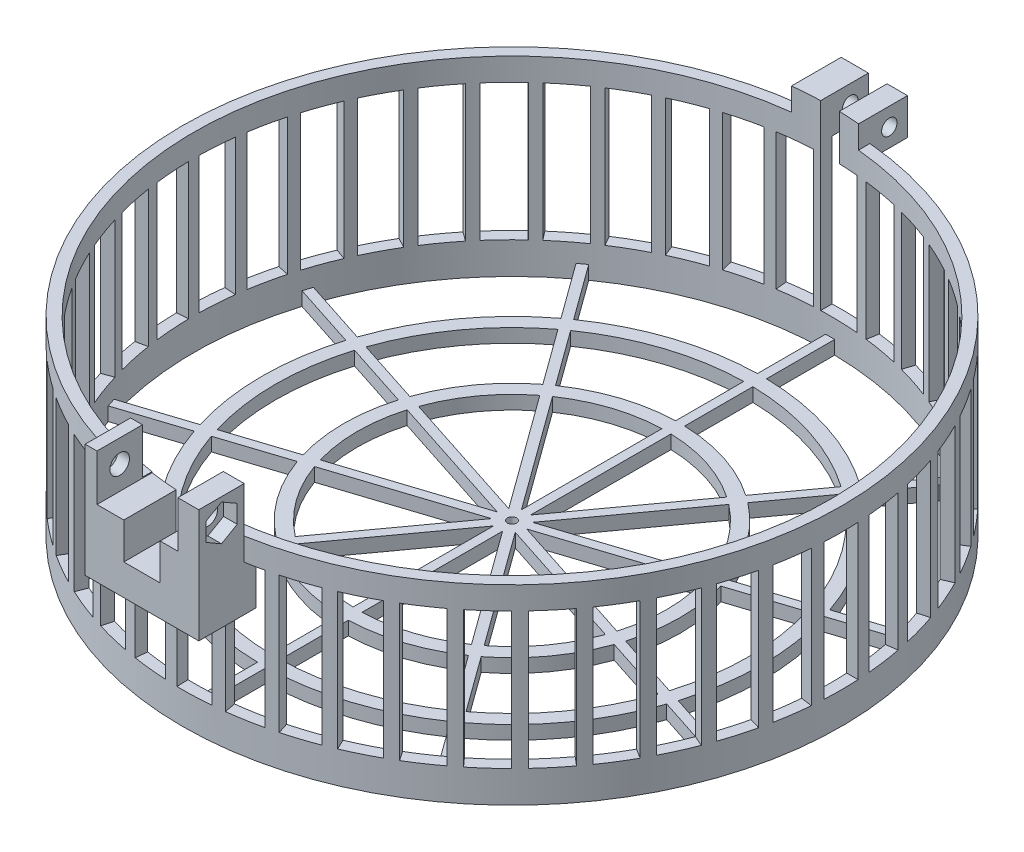
SolidWorks part; units mm, degrees
ref_plane "Front Plane" through (0, 0, 0) normal (0, 0, 1) x (1, 0, 0)
ref_plane "Top Plane" through (0, 0, 0) normal (0, 1, 0) x (1, 0, 0)
ref_plane "Right Plane" through (0, 0, 0) normal (1, 0, 0) x (0, 0, -1)
sketch "Sketch1" plane through (0, 0, 0) normal (0, 1, 0) x (1, 0, 0)
  line L0 (1, 69.9929) -> (0, 70.9924)
  line L2 (1, 69.9929) -> (1, 3.0777)
  line L4 (-1, 69.9929) -> (-1, 3.0777)
  line L5 (-0.8687, 69.9946) -> (-0.1565, 47.2626) construction
  line L7 (0, 70.9924) -> (-1, 69.9929)
  line L8 (41.7283, 57.4341) -> (40.3318, 57.2132)
  line L9 (41.9498, 56.0376) -> (41.7283, 57.4341)
  line L10 (41.9498, 56.0376) -> (2.618, 1.9021)
  line L11 (40.3318, 57.2132) -> (1, 3.0777)
  line L12 (67.5178, 21.9379) -> (66.2581, 22.58)
  line L13 (66.8762, 20.6779) -> (67.5178, 21.9379)
  line L14 (66.8762, 20.6779) -> (3.2361, 0)
  line L15 (66.2581, 22.58) -> (2.618, 1.9021)
  line L16 (67.5178, -21.9379) -> (66.8762, -20.6779)
  line L17 (66.2581, -22.58) -> (67.5178, -21.9379)
  line L18 (66.2581, -22.58) -> (2.618, -1.9021)
  line L19 (66.8762, -20.6779) -> (3.2361, 0)
  line L20 (41.7283, -57.4341) -> (41.9498, -56.0376)
  line L21 (40.3318, -57.2132) -> (41.7283, -57.4341)
  line L22 (40.3318, -57.2132) -> (1, -3.0777)
  line L23 (41.9498, -56.0376) -> (2.618, -1.9021)
  line L24 (0, -70.9924) -> (1, -69.9929)
  line L25 (-1, -69.9929) -> (0, -70.9924)
  line L26 (-1, -69.9929) -> (-1, -3.0777)
  line L27 (1, -69.9929) -> (1, -3.0777)
  line L28 (-41.7283, -57.4341) -> (-40.3318, -57.2132)
  line L29 (-41.9498, -56.0376) -> (-41.7283, -57.4341)
  line L30 (-41.9498, -56.0376) -> (-2.618, -1.9021)
  line L31 (-40.3318, -57.2132) -> (-1, -3.0777)
  line L32 (-67.5178, -21.9379) -> (-66.2581, -22.58)
  line L33 (-66.8762, -20.6779) -> (-67.5178, -21.9379)
  line L34 (-66.8762, -20.6779) -> (-3.2361, 0)
  line L35 (-66.2581, -22.58) -> (-2.618, -1.9021)
  line L36 (-67.5178, 21.9379) -> (-66.8762, 20.6779)
  line L37 (-66.2581, 22.58) -> (-67.5178, 21.9379)
  line L38 (-66.2581, 22.58) -> (-2.618, 1.9021)
  line L39 (-66.8762, 20.6779) -> (-3.2361, 0)
  line L40 (-41.7283, 57.4341) -> (-41.9498, 56.0376)
  line L41 (-40.3318, 57.2132) -> (-41.7283, 57.4341)
  line L42 (-40.3318, 57.2132) -> (-1, 3.0777)
  line L43 (-41.9498, 56.0376) -> (-2.618, 1.9021)
  line L60 (-0.1565, 47.2626) -> (0.8687, 69.9946) construction
  circle A0 centre (0, 0) radius 72.5
  circle A1 centre (0, 0) radius 70
  point P4 (0, 42.2662)
  point P59 (0, 0)
  dimension "D1" = 145
  dimension "D2" = 140
  dimension "D4" = 2
  dimension "D3" = 10
extrude "Boss-Extrude4" add sketch "Sketch1" along normal blind 16 contours A0 | A1
extrude "Boss-Extrude5" add sketch "Sketch1<11>" along normal blind 3 contours L26 L25 L24 L27 L22 L21 L20 L23 L18 L17 L16 L19 L14 L13 L12 L15 L10 L9 L8 L11 L2 L0 L7 L4 L42 L41 L40 L43 L38 L37 L36 L39 L34 L33 L32 L35 L30 L29 L28 L31
sketch "Sketch1<11>" plane through (0, 0, 0) normal (0, 1, 0) x (1, 0, 0) same geometry as "Sketch1"
sketch "Sketch2" plane through (0, 0, 0) normal (0, -1, 0) x (1, 0, 0)
  circle A0 centre (0, 0) radius 1
extrude "Cut-Extrude1" cut sketch "Sketch2" against normal through all
sketch "Sketch3" plane through (0, 0, 0) normal (0, -1, 0) x (1, 0, 0)
  circle A0 centre (0, 0) radius 52
  circle A1 centre (0, 0) radius 55
  circle A2 centre (0, 0) radius 70 construction
  circle A3 centre (0, 0) radius 37
  circle A4 centre (0, 0) radius 34
  dimension "D1" = 3
  dimension "D2" = 15
  dimension "D3" = 3
  dimension "D4" = 15
extrude "Boss-Extrude6" add sketch "Sketch3" against normal up to surface (3 mm away) contours A0 | A1 up to face at (0, 3, -1)
extrude "Boss-Extrude7" add sketch "Sketch1<12>" along normal blind 42 contours A1 | A0
sketch "Sketch1<12>" plane through (0, 0, 0) normal (0, 1, 0) x (1, 0, 0) same geometry as "Sketch1"
extrude "Boss-Extrude13" add sketch "Sketch3<5>" against normal up to surface (3 mm away) contours A3 | A4 up to face at (0, 3, 0)
sketch "Sketch3<5>" plane through (0, 0, 0) normal (0, -1, 0) x (1, 0, 0) same geometry as "Sketch3"
sketch "Sketch25" plane through (0, 42, 0) normal (0, 1, 0) x (1, 0, 0)
  line L0 (-1000, 0) -> (49000, 0) construction
  line L2 (69, 3.75) -> (74, 3.75)
  line L3 (69, 3.75) -> (69, -3.75)
  line L4 (69, -3.75) -> (74, -3.75)
  line L5 (74, 3.75) -> (74, -3.75)
  line L6 (69, 3.75) -> (74, -3.75) construction
  line L7 (69, -3.75) -> (74, 3.75) construction
  line L8 (68.8504, -5.8894) -> (73.8017, -6.5853)
  line L9 (68.8504, -5.8894) -> (67.8066, -13.3164)
  line L10 (67.8066, -13.3164) -> (72.7579, -14.0123)
  line L11 (73.8017, -6.5853) -> (72.7579, -14.0123)
  line L12 (68.8504, -5.8894) -> (72.7579, -14.0123) construction
  line L13 (67.8066, -13.3164) -> (73.8017, -6.5853) construction
  line L14 (67.3607, -15.4142) -> (72.167, -16.7924)
  line L15 (67.3607, -15.4142) -> (65.2934, -22.6237)
  line L16 (65.2934, -22.6237) -> (70.0997, -24.0019)
  line L17 (72.167, -16.7924) -> (70.0997, -24.0019)
  line L18 (67.3607, -15.4142) -> (70.0997, -24.0019) construction
  line L19 (65.2934, -22.6237) -> (72.167, -16.7924) construction
  line L20 (64.5599, -24.639) -> (69.1276, -26.6727)
  line L21 (64.5599, -24.639) -> (61.5094, -31.4906)
  line L22 (61.5094, -31.4906) -> (66.0771, -33.5243)
  line L23 (69.1276, -26.6727) -> (66.0771, -33.5243)
  line L24 (64.5599, -24.639) -> (66.0771, -33.5243) construction
  line L25 (61.5094, -31.4906) -> (69.1276, -26.6727) construction
  line L26 (60.5025, -33.3842) -> (64.7428, -36.0338)
  line L27 (60.5025, -33.3842) -> (56.5281, -39.7446)
  line L28 (56.5281, -39.7446) -> (60.7684, -42.3942)
  line L29 (64.7428, -36.0338) -> (60.7684, -42.3942)
  line L30 (60.5025, -33.3842) -> (60.7684, -42.3942) construction
  line L31 (56.5281, -39.7446) -> (64.7428, -36.0338) construction
  line L32 (55.2675, -41.4797) -> (59.0977, -44.6936)
  line L33 (55.2675, -41.4797) -> (50.4466, -47.225)
  line L34 (50.4466, -47.225) -> (54.2768, -50.4389)
  line L35 (59.0977, -44.6936) -> (54.2768, -50.4389)
  line L36 (55.2675, -41.4797) -> (54.2768, -50.4389) construction
  line L37 (50.4466, -47.225) -> (59.0977, -44.6936) construction
  line L38 (48.9568, -48.7678) -> (52.3025, -52.4835)
  line L39 (48.9568, -48.7678) -> (43.3832, -53.7862)
  line L40 (43.3832, -53.7862) -> (46.7289, -57.502)
  line L41 (52.3025, -52.4835) -> (46.7289, -57.502)
  line L42 (48.9568, -48.7678) -> (46.7289, -57.502) construction
  line L43 (43.3832, -53.7862) -> (52.3025, -52.4835) construction
  line L44 (41.6932, -55.1066) -> (44.4892, -59.2518)
  line L45 (41.6932, -55.1066) -> (35.4754, -59.3006)
  line L46 (35.4754, -59.3006) -> (38.2714, -63.4458)
  line L47 (44.4892, -59.2518) -> (38.2714, -63.4458)
  line L48 (41.6932, -55.1066) -> (38.2714, -63.4458) construction
  line L49 (35.4754, -59.3006) -> (44.4892, -59.2518) construction
  line L50 (33.6181, -60.3729) -> (35.8099, -64.8669)
  line L51 (33.6181, -60.3729) -> (26.8771, -63.6607)
  line L52 (26.8771, -63.6607) -> (29.069, -68.1547)
  line L53 (35.8099, -64.8669) -> (29.069, -68.1547)
  line L54 (33.6181, -60.3729) -> (29.069, -68.1547) construction
  line L55 (26.8771, -63.6607) -> (35.8099, -64.8669) construction
  line L56 (24.8886, -64.4641) -> (26.4337, -69.2194)
  line L57 (24.8886, -64.4641) -> (17.7557, -66.7817)
  line L58 (17.7557, -66.7817) -> (19.3008, -71.537)
  line L59 (26.4337, -69.2194) -> (19.3008, -71.537)
  line L60 (24.8886, -64.4641) -> (19.3008, -71.537) construction
  line L61 (17.7557, -66.7817) -> (26.4337, -69.2194) construction
  line L62 (15.6748, -67.3006) -> (16.543, -72.2246)
  line L63 (15.6748, -67.3006) -> (8.2887, -68.6029)
  line L64 (8.2887, -68.6029) -> (9.1569, -73.527)
  line L65 (16.543, -72.2246) -> (9.1569, -73.527)
  line L66 (15.6748, -67.3006) -> (9.1569, -73.527) construction
  line L67 (8.2887, -68.6029) -> (16.543, -72.2246) construction
  line L68 (6.1558, -68.8271) -> (6.3303, -73.824)
  line L69 (6.1558, -68.8271) -> (-1.3397, -69.0888)
  line L70 (-1.3397, -69.0888) -> (-1.1652, -74.0858)
  line L71 (6.3303, -73.824) -> (-1.1652, -74.0858)
  line L72 (6.1558, -68.8271) -> (-1.1652, -74.0858) construction
  line L73 (-1.3397, -69.0888) -> (6.3303, -73.824) construction
  line L74 (-3.483, -69.014) -> (-4.0056, -73.9866)
  line L75 (-3.483, -69.014) -> (-10.9419, -68.23)
  line L76 (-10.9419, -68.23) -> (-11.4646, -73.2026)
  line L77 (-4.0056, -73.9866) -> (-11.4646, -73.2026)
  line L78 (-3.483, -69.014) -> (-11.4646, -73.2026) construction
  line L79 (-10.9419, -68.23) -> (-4.0056, -73.9866) construction
  line L80 (-13.054, -67.8576) -> (-14.2636, -72.7091)
  line L81 (-13.054, -67.8576) -> (-20.3312, -66.0432)
  line L82 (-20.3312, -66.0432) -> (-21.5408, -70.8947)
  line L83 (-14.2636, -72.7091) -> (-21.5408, -70.8947)
  line L84 (-13.054, -67.8576) -> (-21.5408, -70.8947) construction
  line L85 (-20.3312, -66.0432) -> (-14.2636, -72.7091) construction
  line L86 (-22.3709, -65.3805) -> (-24.2439, -70.0164)
  line L87 (-22.3709, -65.3805) -> (-29.3248, -62.5709)
  line L88 (-29.3248, -62.5709) -> (-31.1978, -67.2068)
  line L89 (-24.2439, -70.0164) -> (-31.1978, -67.2068)
  line L90 (-22.3709, -65.3805) -> (-31.1978, -67.2068) construction
  line L91 (-29.3248, -62.5709) -> (-24.2439, -70.0164) construction
  line L92 (-31.2524, -61.6308) -> (-33.7524, -65.9609)
  line L93 (-31.2524, -61.6308) -> (-37.7476, -57.8808)
  line L94 (-37.7476, -57.8808) -> (-40.2476, -62.2109)
  line L95 (-33.7524, -65.9609) -> (-40.2476, -62.2109)
  line L96 (-31.2524, -61.6308) -> (-40.2476, -62.2109) construction
  line L97 (-37.7476, -57.8808) -> (-33.7524, -65.9609) construction
  line L98 (-39.5256, -56.6815) -> (-42.6039, -60.6215)
  line L99 (-39.5256, -56.6815) -> (-45.4357, -52.064)
  line L100 (-45.4357, -52.064) -> (-48.514, -56.0041)
  line L101 (-42.6039, -60.6215) -> (-48.514, -56.0041)
  line L102 (-39.5256, -56.6815) -> (-48.514, -56.0041) construction
  line L103 (-45.4357, -52.064) -> (-42.6039, -60.6215) construction
  line L104 (-47.0295, -50.629) -> (-50.6262, -54.1022)
  line L105 (-47.0295, -50.629) -> (-52.2394, -45.2339)
  line L106 (-52.2394, -45.2339) -> (-55.8361, -48.7072)
  line L107 (-50.6262, -54.1022) -> (-55.8361, -48.7072)
  line L108 (-47.0295, -50.629) -> (-55.8361, -48.7072) construction
  line L109 (-52.2394, -45.2339) -> (-50.6262, -54.1022) construction
  line L110 (-53.618, -43.591) -> (-57.6631, -46.5299)
  line L111 (-53.618, -43.591) -> (-58.0264, -37.5234)
  line L112 (-58.0264, -37.5234) -> (-62.0715, -40.4623)
  line L113 (-57.6631, -46.5299) -> (-62.0715, -40.4623)
  line L114 (-53.618, -43.591) -> (-62.0715, -40.4623) construction
  line L115 (-58.0264, -37.5234) -> (-57.6631, -46.5299) construction
  line L116 (-59.1629, -35.7046) -> (-63.5776, -38.0519)
  line L117 (-59.1629, -35.7046) -> (-62.6839, -29.0825)
  line L118 (-62.6839, -29.0825) -> (-67.0986, -31.4298)
  line L119 (-63.5776, -38.0519) -> (-67.0986, -31.4298)
  line L120 (-59.1629, -35.7046) -> (-67.0986, -31.4298) construction
  line L121 (-62.6839, -29.0825) -> (-63.5776, -38.0519) construction
  line L122 (-63.5562, -27.1232) -> (-68.2547, -28.8333)
  line L123 (-63.5562, -27.1232) -> (-66.1214, -20.0755)
  line L124 (-66.1214, -20.0755) -> (-70.8198, -21.7856)
  line L125 (-68.2547, -28.8333) -> (-70.8198, -21.7856)
  line L126 (-63.5562, -27.1232) -> (-70.8198, -21.7856) construction
  line L127 (-66.1214, -20.0755) -> (-68.2547, -28.8333) construction
  line L128 (-66.7125, -18.014) -> (-71.6033, -19.0535)
  line L129 (-66.7125, -18.014) -> (-68.2719, -10.6779)
  line L130 (-68.2719, -10.6779) -> (-73.1626, -11.7174)
  line L131 (-71.6033, -19.0535) -> (-73.1626, -11.7174)
  line L132 (-66.7125, -18.014) -> (-73.1626, -11.7174) construction
  line L133 (-68.2719, -10.6779) -> (-71.6033, -19.0535) construction
  line L134 (-68.5703, -8.5541) -> (-73.5582, -8.9028)
  line L135 (-68.5703, -8.5541) -> (-69.0935, -1.0723)
  line L136 (-69.0935, -1.0723) -> (-74.0813, -1.4211)
  line L137 (-73.5582, -8.9028) -> (-74.0813, -1.4211)
  line L138 (-68.5703, -8.5541) -> (-74.0813, -1.4211) construction
  line L139 (-69.0935, -1.0723) -> (-73.5582, -8.9028) construction
  line L140 (-69.0935, 1.0723) -> (-74.0813, 1.4211)
  line L141 (-69.0935, 1.0723) -> (-68.5703, 8.5541)
  line L142 (-68.5703, 8.5541) -> (-73.5582, 8.9028)
  line L143 (-74.0813, 1.4211) -> (-73.5582, 8.9028)
  line L144 (-69.0935, 1.0723) -> (-73.5582, 8.9028) construction
  line L145 (-68.5703, 8.5541) -> (-74.0813, 1.4211) construction
  line L146 (-68.2719, 10.6779) -> (-73.1626, 11.7174)
  line L147 (-68.2719, 10.6779) -> (-66.7125, 18.014)
  line L148 (-66.7125, 18.014) -> (-71.6033, 19.0535)
  line L149 (-73.1626, 11.7174) -> (-71.6033, 19.0535)
  line L150 (-68.2719, 10.6779) -> (-71.6033, 19.0535) construction
  line L151 (-66.7125, 18.014) -> (-73.1626, 11.7174) construction
  line L152 (-66.1214, 20.0755) -> (-70.8198, 21.7856)
  line L153 (-66.1214, 20.0755) -> (-63.5562, 27.1232)
  line L154 (-63.5562, 27.1232) -> (-68.2547, 28.8333)
  line L155 (-70.8198, 21.7856) -> (-68.2547, 28.8333)
  line L156 (-66.1214, 20.0755) -> (-68.2547, 28.8333) construction
  line L157 (-63.5562, 27.1232) -> (-70.8198, 21.7856) construction
  line L158 (-62.6839, 29.0825) -> (-67.0986, 31.4298)
  line L159 (-62.6839, 29.0825) -> (-59.1629, 35.7046)
  line L160 (-59.1629, 35.7046) -> (-63.5776, 38.0519)
  line L161 (-67.0986, 31.4298) -> (-63.5776, 38.0519)
  line L162 (-62.6839, 29.0825) -> (-63.5776, 38.0519) construction
  line L163 (-59.1629, 35.7046) -> (-67.0986, 31.4298) construction
  line L164 (-58.0264, 37.5234) -> (-62.0715, 40.4623)
  line L165 (-58.0264, 37.5234) -> (-53.618, 43.591)
  line L166 (-53.618, 43.591) -> (-57.6631, 46.5299)
  line L167 (-62.0715, 40.4623) -> (-57.6631, 46.5299)
  line L168 (-58.0264, 37.5234) -> (-57.6631, 46.5299) construction
  line L169 (-53.618, 43.591) -> (-62.0715, 40.4623) construction
  line L170 (-52.2394, 45.2339) -> (-55.8361, 48.7072)
  line L171 (-52.2394, 45.2339) -> (-47.0295, 50.629)
  line L172 (-47.0295, 50.629) -> (-50.6262, 54.1022)
  line L173 (-55.8361, 48.7072) -> (-50.6262, 54.1022)
  line L174 (-52.2394, 45.2339) -> (-50.6262, 54.1022) construction
  line L175 (-47.0295, 50.629) -> (-55.8361, 48.7072) construction
  line L176 (-45.4357, 52.064) -> (-48.514, 56.0041)
  line L177 (-45.4357, 52.064) -> (-39.5256, 56.6815)
  line L178 (-39.5256, 56.6815) -> (-42.6039, 60.6215)
  line L179 (-48.514, 56.0041) -> (-42.6039, 60.6215)
  line L180 (-45.4357, 52.064) -> (-42.6039, 60.6215) construction
  line L181 (-39.5256, 56.6815) -> (-48.514, 56.0041) construction
  line L182 (-37.7476, 57.8808) -> (-40.2476, 62.2109)
  line L183 (-37.7476, 57.8808) -> (-31.2524, 61.6308)
  line L184 (-31.2524, 61.6308) -> (-33.7524, 65.9609)
  line L185 (-40.2476, 62.2109) -> (-33.7524, 65.9609)
  line L186 (-37.7476, 57.8808) -> (-33.7524, 65.9609) construction
  line L187 (-31.2524, 61.6308) -> (-40.2476, 62.2109) construction
  line L188 (-29.3248, 62.5709) -> (-31.1978, 67.2068)
  line L189 (-29.3248, 62.5709) -> (-22.3709, 65.3805)
  line L190 (-22.3709, 65.3805) -> (-24.2439, 70.0164)
  line L191 (-31.1978, 67.2068) -> (-24.2439, 70.0164)
  line L192 (-29.3248, 62.5709) -> (-24.2439, 70.0164) construction
  line L193 (-22.3709, 65.3805) -> (-31.1978, 67.2068) construction
  line L194 (-20.3312, 66.0432) -> (-21.5408, 70.8947)
  line L195 (-20.3312, 66.0432) -> (-13.054, 67.8576)
  line L196 (-13.054, 67.8576) -> (-14.2636, 72.7091)
  line L197 (-21.5408, 70.8947) -> (-14.2636, 72.7091)
  line L198 (-20.3312, 66.0432) -> (-14.2636, 72.7091) construction
  line L199 (-13.054, 67.8576) -> (-21.5408, 70.8947) construction
  line L200 (-10.9419, 68.23) -> (-11.4646, 73.2026)
  line L201 (-10.9419, 68.23) -> (-3.483, 69.014)
  line L202 (-3.483, 69.014) -> (-4.0056, 73.9866)
  line L203 (-11.4646, 73.2026) -> (-4.0056, 73.9866)
  line L204 (-10.9419, 68.23) -> (-4.0056, 73.9866) construction
  line L205 (-3.483, 69.014) -> (-11.4646, 73.2026) construction
  line L206 (-1.3397, 69.0888) -> (-1.1652, 74.0858)
  line L207 (-1.3397, 69.0888) -> (6.1558, 68.8271)
  line L208 (6.1558, 68.8271) -> (6.3303, 73.824)
  line L209 (-1.1652, 74.0858) -> (6.3303, 73.824)
  line L210 (-1.3397, 69.0888) -> (6.3303, 73.824) construction
  line L211 (6.1558, 68.8271) -> (-1.1652, 74.0858) construction
  line L212 (8.2887, 68.6029) -> (9.1569, 73.527)
  line L213 (8.2887, 68.6029) -> (15.6748, 67.3006)
  line L214 (15.6748, 67.3006) -> (16.543, 72.2246)
  line L215 (9.1569, 73.527) -> (16.543, 72.2246)
  line L216 (8.2887, 68.6029) -> (16.543, 72.2246) construction
  line L217 (15.6748, 67.3006) -> (9.1569, 73.527) construction
  line L218 (17.7557, 66.7817) -> (19.3008, 71.537)
  line L219 (17.7557, 66.7817) -> (24.8886, 64.4641)
  line L220 (24.8886, 64.4641) -> (26.4337, 69.2194)
  line L221 (19.3008, 71.537) -> (26.4337, 69.2194)
  line L222 (17.7557, 66.7817) -> (26.4337, 69.2194) construction
  line L223 (24.8886, 64.4641) -> (19.3008, 71.537) construction
  line L224 (26.8771, 63.6607) -> (29.069, 68.1547)
  line L225 (26.8771, 63.6607) -> (33.6181, 60.3729)
  line L226 (33.6181, 60.3729) -> (35.8099, 64.8669)
  line L227 (29.069, 68.1547) -> (35.8099, 64.8669)
  line L228 (26.8771, 63.6607) -> (35.8099, 64.8669) construction
  line L229 (33.6181, 60.3729) -> (29.069, 68.1547) construction
  line L230 (35.4754, 59.3006) -> (38.2714, 63.4458)
  line L231 (35.4754, 59.3006) -> (41.6932, 55.1066)
  line L232 (41.6932, 55.1066) -> (44.4892, 59.2518)
  line L233 (38.2714, 63.4458) -> (44.4892, 59.2518)
  line L234 (35.4754, 59.3006) -> (44.4892, 59.2518) construction
  line L235 (41.6932, 55.1066) -> (38.2714, 63.4458) construction
  line L236 (43.3832, 53.7862) -> (46.7289, 57.502)
  line L237 (43.3832, 53.7862) -> (48.9568, 48.7678)
  line L238 (48.9568, 48.7678) -> (52.3025, 52.4835)
  line L239 (46.7289, 57.502) -> (52.3025, 52.4835)
  line L240 (43.3832, 53.7862) -> (52.3025, 52.4835) construction
  line L241 (48.9568, 48.7678) -> (46.7289, 57.502) construction
  line L242 (50.4466, 47.225) -> (54.2768, 50.4389)
  line L243 (50.4466, 47.225) -> (55.2675, 41.4797)
  line L244 (55.2675, 41.4797) -> (59.0977, 44.6936)
  line L245 (54.2768, 50.4389) -> (59.0977, 44.6936)
  line L246 (50.4466, 47.225) -> (59.0977, 44.6936) construction
  line L247 (55.2675, 41.4797) -> (54.2768, 50.4389) construction
  line L248 (56.5281, 39.7446) -> (60.7684, 42.3942)
  line L249 (56.5281, 39.7446) -> (60.5025, 33.3842)
  line L250 (60.5025, 33.3842) -> (64.7428, 36.0338)
  line L251 (60.7684, 42.3942) -> (64.7428, 36.0338)
  line L252 (56.5281, 39.7446) -> (64.7428, 36.0338) construction
  line L253 (60.5025, 33.3842) -> (60.7684, 42.3942) construction
  line L254 (61.5094, 31.4906) -> (66.0771, 33.5243)
  line L255 (61.5094, 31.4906) -> (64.5599, 24.639)
  line L256 (64.5599, 24.639) -> (69.1276, 26.6727)
  line L257 (66.0771, 33.5243) -> (69.1276, 26.6727)
  line L258 (61.5094, 31.4906) -> (69.1276, 26.6727) construction
  line L259 (64.5599, 24.639) -> (66.0771, 33.5243) construction
  line L260 (65.2934, 22.6237) -> (70.0997, 24.0019)
  line L261 (65.2934, 22.6237) -> (67.3607, 15.4142)
  line L262 (67.3607, 15.4142) -> (72.167, 16.7924)
  line L263 (70.0997, 24.0019) -> (72.167, 16.7924)
  line L264 (65.2934, 22.6237) -> (72.167, 16.7924) construction
  line L265 (67.3607, 15.4142) -> (70.0997, 24.0019) construction
  line L266 (67.8066, 13.3164) -> (72.7579, 14.0123)
  line L267 (67.8066, 13.3164) -> (68.8504, 5.8894)
  line L268 (68.8504, 5.8894) -> (73.8017, 6.5853)
  line L269 (72.7579, 14.0123) -> (73.8017, 6.5853)
  line L270 (67.8066, 13.3164) -> (73.8017, 6.5853) construction
  line L271 (68.8504, 5.8894) -> (72.7579, 14.0123) construction
  circle A0 centre (0, 0) radius 70 construction
  point P1 (71.5, 0)
  point P8 (70.8042, -9.9509)
  point P17 (68.7302, -19.7081)
  point P22 (65.3185, -29.0817)
  point P27 (60.6354, -37.8892)
  point P32 (54.7722, -45.9593)
  point P37 (47.8428, -53.1349)
  point P42 (39.9823, -59.2762)
  point P47 (31.3435, -64.2638)
  point P52 (22.0947, -68.0005)
  point P57 (12.4158, -70.4138)
  point P62 (2.4953, -71.4564)
  point P67 (-7.4738, -71.1083)
  point P72 (-17.2974, -69.3761)
  point P77 (-26.7844, -66.2936)
  point P82 (-35.75, -61.9208)
  point P87 (-44.0198, -56.3428)
  point P92 (-51.4328, -49.6681)
  point P97 (-57.8447, -42.0266)
  point P102 (-63.1308, -33.5672)
  point P107 (-67.188, -24.4544)
  point P112 (-69.9376, -14.8657)
  point P117 (-71.3258, -4.9876)
  point P122 (-71.3258, 4.9876)
  point P127 (-69.9376, 14.8657)
  point P132 (-67.188, 24.4544)
  point P137 (-63.1308, 33.5672)
  point P142 (-57.8447, 42.0266)
  point P147 (-51.4328, 49.6681)
  point P152 (-44.0198, 56.3428)
  point P157 (-35.75, 61.9208)
  point P162 (-26.7844, 66.2936)
  point P167 (-17.2974, 69.3761)
  point P172 (-7.4738, 71.1083)
  point P177 (2.4953, 71.4564)
  point P182 (12.4158, 70.4138)
  point P185 (0, 0)
  point P188 (22.0947, 68.0005)
  point P193 (31.3435, 64.2638)
  point P198 (39.9823, 59.2762)
  point P203 (47.8428, 53.1349)
  point P208 (54.7722, 45.9593)
  point P213 (60.6354, 37.8892)
  point P218 (65.3185, 29.0817)
  point P223 (68.7302, 19.7081)
  point P228 (70.8042, 9.9509)
  point P233 (0, 0)
  dimension "D3" = 71.5
  dimension "D1" = 7.5
  dimension "D2" = 5
extrude "Cut-Extrude11" cut sketch "Sketch25" against normal blind 35
sketch "Sketch27" plane through (0, 42, 0) normal (0, 1, 0) x (1, 0, 0)
  circle A0 centre (0, 0) radius 72.5
  circle A1 centre (0, 0) radius 70
extrude "Boss-Extrude14" add sketch "Sketch27" against normal blind 5
sketch "Sketch28" plane through (0, 42, 0) normal (0, 1, 0) x (1, 0, 0)
  line L0 (2.05, 80.471) -> (6.55, 80.471)
  line L15 (-2.05, 72.471) -> (-2.05, 80.471) construction
  line L16 (-2.05, 80.471) -> (2.05, 80.471) construction
  line L17 (2.05, 72.471) -> (2.05, 80.471) construction
  line L18 (-2.05, 72.471) -> (2.05, 80.471) construction
  line L19 (-2.05, 80.471) -> (2.05, 72.471) construction
  line L20 (6.55, 80.471) -> (6.55, 69.6929)
  line L21 (-2.05, 72.471) -> (-2.05, 80.471)
  line L22 (-2.05, 80.471) -> (-8.05, 80.471)
  line L23 (-8.05, 80.471) -> (-8.05, 72.0517)
  line L24 (2.05, 80.471) -> (2.05, 72.471)
  line L26 (-8.05, 72.0517) -> (-8.05, 69.5356)
  line L27 (-2.05, 72.471) -> (-2.05, 69.97)
  line L28 (2.05, 72.471) -> (2.05, 69.97)
  arc A0 (-8.05, 69.5356) -> (-2.05, 69.97) centre (0, 0) cw
  circle A2 centre (0, 0) radius 72.5 construction
  circle A4 centre (0, 0) radius 70 construction
  arc A6 (2.05, 69.97) -> (6.55, 69.6929) centre (0, 0) cw
  point P0 (0, 76.471)
  dimension "D5" = 70
  dimension "D6" = 8
  dimension "D1" = 4.1
  dimension "D2" = 8
  dimension "D3" = 6
  dimension "D4" = 4.5
extrude "Boss-Extrude15" add sketch "Sketch28" along normal blind 8 from offset 3 offset against normal yes
sketch "Sketch30" plane through (0, 42, 0) normal (0, 1, 0) x (1, 0, 0)
  line L1 (-2.05, 73.4714) -> (2.05, 73.4714)
  line L2 (-2.05, 73.4714) -> (-2.05, 69.4714)
  line L3 (-2.05, 69.4714) -> (2.05, 69.4714)
  line L4 (2.05, 73.4714) -> (2.05, 69.4714)
  line L5 (-2.05, 73.4714) -> (2.05, 69.4714) construction
  line L6 (-2.05, 69.4714) -> (2.05, 73.4714) construction
  line L7 (-2.05, 72.471) -> (-2.05, 80.471) construction
  line L8 (2.05, 80.471) -> (2.05, 72.471) construction
  arc A0 (2.05, 72.471) -> (-2.05, 72.471) centre (0, 0) ccw construction
  point P4 (0, 71.4714)
  dimension "D1" = 4
  dimension "D2" = 73.5
extrude "Cut-Extrude13" cut sketch "Sketch30" against normal up to surface (35 mm away) up to face at (2.4849, 7, -71.1572)
sketch "Sketch33" plane through (0, 42, 0) normal (0, 1, 0) x (1, 0, 0)
  line L1 (12.5, -71.4143) -> (-12.5, -71.4143) construction
  line L2 (12.5, -71.4143) -> (12.5, -121.4143) construction
  line L3 (12.5, -121.4143) -> (-12.5, -121.4143) construction
  line L4 (-12.5, -71.4143) -> (-12.5, -121.4143) construction
  line L5 (12.5, -71.4143) -> (-12.5, -121.4143) construction
  line L6 (12.5, -121.4143) -> (-12.5, -71.4143) construction
  line L7 (12.5, -71.4143) -> (7.9, -71.4143)
  line L8 (12.5, -71.4143) -> (12.5, -81.4143)
  line L9 (12.5, -81.4143) -> (7.9, -81.4143)
  line L10 (7.9, -71.4143) -> (7.9, -81.4143)
  line L11 (12.5, -71.4143) -> (7.9, -81.4143) construction
  line L12 (12.5, -81.4143) -> (7.9, -71.4143) construction
  line L13 (-12.5, -71.4143) -> (-9.9, -71.4143)
  line L14 (-12.5, -71.4143) -> (-12.5, -81.4143)
  line L15 (-12.5, -81.4143) -> (-9.9, -81.4143)
  line L16 (-9.9, -71.4143) -> (-9.9, -81.4143)
  line L17 (-12.5, -71.4143) -> (-9.9, -81.4143) construction
  line L18 (-12.5, -81.4143) -> (-9.9, -71.4143) construction
  arc A0 (-8.05, 72.0517) -> (6.55, 72.2035) centre (0, 0) ccw construction
  point P0 (0, -96.4143)
  point P15 (10.2, -76.4143)
  point P16 (-11.2, -76.4143)
  dimension "D1" = 25
  dimension "D2" = 50
  dimension "D3" = 4.6
  dimension "D4" = 2.6
  dimension "D5" = 10
extrude "Boss-Extrude17" add sketch "Sketch33" along normal blind 10
sketch "Sketch34" plane through (0, 42, 0) normal (0, -1, 0) x (1, 0, 0)
  line L1 (-12.5, 81.4143) -> (12.5, 81.4143)
  line L2 (-12.5, 81.4143) -> (-12.5, 71.4143)
  line L3 (-12.5, 71.4143) -> (12.5, 71.4143)
  line L4 (12.5, 81.4143) -> (12.5, 71.4143)
  line L5 (-12.5, 81.4143) -> (12.5, 71.4143) construction
  line L6 (-12.5, 71.4143) -> (12.5, 81.4143) construction
  point P4 (0, 76.4143)
extrude "Boss-Extrude18" add sketch "Sketch34" along normal up to surface (5 mm away) up to face at (12.3639, 37, 70.1189)
sketch "Sketch35" plane through (-8.05, 0, 0) normal (-1, 0, 0) x (0, 0, 1)
  line L0 (71.4143, 52) -> (71.4143, 42) construction
  line L1 (-80.471, 47) -> (-72.471, 47) construction
  line L2 (-80.471, 47) -> (-80.471, 39) construction
  line L3 (-80.471, 39) -> (-72.471, 39) construction
  line L4 (-72.471, 47) -> (-72.471, 39) construction
  line L5 (-80.471, 47) -> (-72.471, 39) construction
  line L6 (-80.471, 39) -> (-72.471, 47) construction
  line L7 (81.4143, 52) -> (71.4143, 52) construction
  line L8 (81.4143, 52) -> (81.4143, 42) construction
  line L9 (81.4143, 42) -> (71.4143, 42) construction
  line L10 (71.4143, 52) -> (71.4143, 42) construction
  line L11 (81.4143, 52) -> (71.4143, 42) construction
  line L12 (81.4143, 42) -> (71.4143, 52) construction
  circle A0 centre (-76.471, 43) radius 1.7
  circle A1 centre (76.4143, 47) radius 2.15
  point P4 (-76.471, 43)
  point P12 (76.4143, 47)
  dimension "D3" = 3.4
  dimension "D5" = 4.3
  dimension "D1" = 8
  dimension "D2" = 8
  dimension "D4" = 10
extrude "Cut-Extrude16" cut sketch "Sketch35" against normal through all both and the other way through all
sketch "Sketch36" plane through (0, 42, 0) normal (0, 1, 0) x (1, 0, 0)
  line L0 (7.9, -71.4143) -> (7.9, -81.4143) construction
  line L1 (-9.9, -81.4143) -> (7.9, -81.4143)
  line L2 (-9.9, -81.4143) -> (-9.9, -69.2964)
  line L3 (-9.9, -69.2964) -> (7.9, -69.2964)
  line L4 (7.9, -81.4143) -> (7.9, -69.2964)
  line L5 (-9.9, -81.4143) -> (7.9, -69.2964) construction
  line L6 (-9.9, -69.2964) -> (7.9, -81.4143) construction
  arc A1 (-8.05, 69.5356) -> (6.55, 69.6929) centre (0, 0) ccw construction
  point P4 (-1, -75.3553)
extrude "Cut-Extrude17" cut sketch "Sketch36" against normal blind 0.2
sketch "Sketch37" plane through (12.5, 0, 0) normal (1, 0, 0) x (0, 0, -1)
  line L1 (-76.4143, 43.0163) -> (-72.9643, 45.0081)
  line L2 (-72.9643, 45.0081) -> (-72.9643, 48.9919)
  line L3 (-72.9643, 48.9919) -> (-76.4143, 50.9837)
  line L4 (-76.4143, 50.9837) -> (-79.8643, 48.9919)
  line L5 (-79.8643, 48.9919) -> (-79.8643, 45.0081)
  line L6 (-79.8643, 45.0081) -> (-76.4143, 43.0163)
  circle A0 centre (-76.4143, 47) radius 3.45 construction
  dimension "D1" = 6.9
sketch "Sketch38" plane through (-8.05, 0, 0) normal (-1, 0, 0) x (0, 0, 1)
  line L1 (-73.771, 44.5588) -> (-76.471, 46.1177)
  line L2 (-76.471, 46.1177) -> (-79.171, 44.5588)
  line L3 (-79.171, 44.5588) -> (-79.171, 41.4412)
  line L4 (-79.171, 41.4412) -> (-76.471, 39.8823)
  line L5 (-76.471, 39.8823) -> (-73.771, 41.4412)
  line L6 (-73.771, 41.4412) -> (-73.771, 44.5588)
  circle A0 centre (-76.471, 43) radius 2.7 construction
  dimension "D1" = 5.4
extrude "Cut-Extrude18" cut sketch "Sketch38" against normal blind 2.5
sketch "Sketch44" plane through (0, 37, 0) normal (0, -1, 0) x (1, 0, 0)
  line L0 (12.5, 72.9643) -> (12.5, 79.8643) construction
  line L1 (-12.5, 81.4143) -> (12.5, 81.4143)
  line L2 (-12.5, 81.4143) -> (-12.5, 68.8749)
  line L4 (12.5, 81.4143) -> (12.5, 68.8749)
  line L5 (-12.5, 81.4143) -> (12.5, 68.8749) construction
  line L6 (-12.5, 68.8749) -> (12.5, 81.4143) construction
  arc A0 (-12.5, 68.8749) -> (12.5, 68.8749) centre (0, 0) cw
  arc A1 (-1, 69.9929) -> (-40.3318, 57.2132) centre (0, 0) ccw construction
  arc A2 (40.3318, 57.2132) -> (1, 69.9929) centre (0, 0) ccw construction
  point P4 (0, 75.1446)
extrude "Boss-Extrude21" add sketch "Sketch44" along normal blind 10
sketch "Sketch45" plane through (0, 41.8, 0) normal (0, 1, 0) x (1, 0, 0)
  line L0 (-9.9, -81.4143) -> (7.9, -81.4143) construction
  line L1 (-4, -81.4143) -> (4, -81.4143)
  line L2 (-4, -81.4143) -> (-4, -69.8856)
  line L3 (-4, -69.8856) -> (4, -69.8856)
  line L4 (4, -81.4143) -> (4, -69.8856)
  line L5 (-4, -81.4143) -> (4, -69.8856) construction
  line L6 (-4, -69.8856) -> (4, -81.4143) construction
  arc A1 (-9.9, -69.2964) -> (7.9, -69.5528) centre (0, 0) ccw construction
  point P4 (0, -75.65)
  dimension "D1" = 8
extrude "Cut-Extrude21" cut sketch "Sketch45" against normal blind 8
extrude "Cut-Extrude22" cut sketch "Sketch37" against normal blind 3
